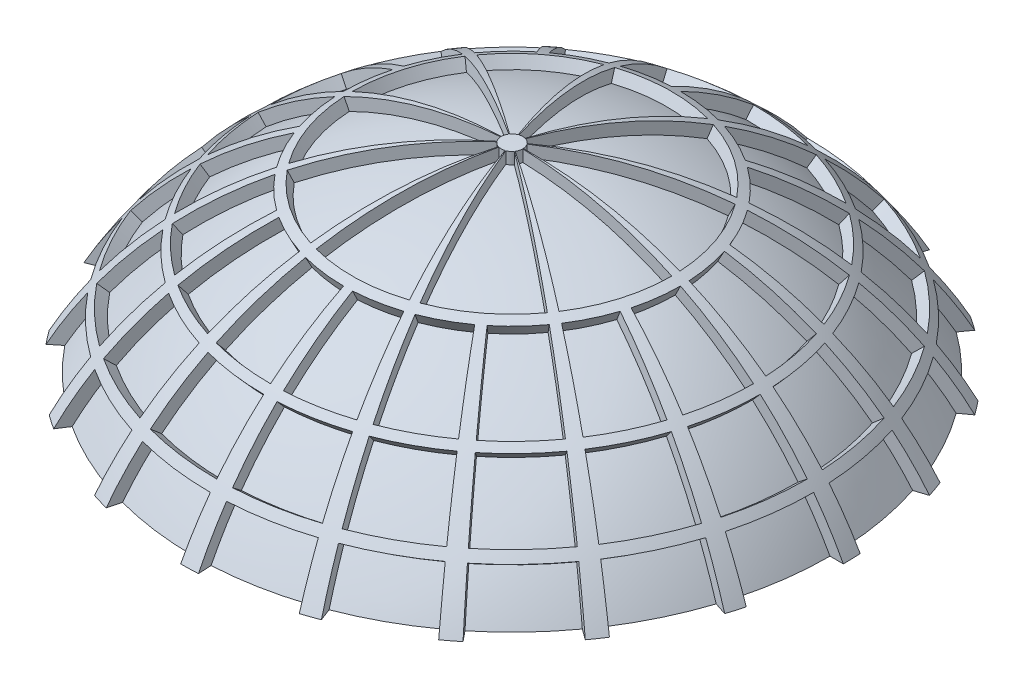
SolidWorks part; units mm, degrees
note: The reader was unsure of these and kept them because the rebuilt part matched: shared geometry of "草图1<3>", "草图1<5>".
ref_plane "前视基准面" through (0, 0, 0) normal (0, 0, 1) x (1, 0, 0)
ref_plane "上视基准面" through (0, 0, 0) normal (0, 1, 0) x (1, 0, 0)
ref_plane "右视基准面" through (0, 0, 0) normal (1, 0, 0) x (0, 0, -1)
sketch "草图1" plane through (0, 0, 0) normal (0, 0, 1) x (1, 0, 0)
  line L0 (0, 300) -> (0, 150)
  line L1 (0, 300) -> (0, 765.499)
  line L2 (0, -300) -> (0, -863.1339)
  line L3 (-10, -300) -> (-10, -863.1339)
  line L4 (0, 150) -> (996.1607, 150)
  line L5 (139.286, 276.9466) -> (143.7791, 285.8803)
  line L6 (132.0893, 280.4504) -> (136.3503, 289.4972)
  line L7 (211.8031, 239.8738) -> (205.1842, 232.3778)
  line L8 (206.0532, 244.8307) -> (199.6141, 237.1797)
  line L9 (257.3478, 190.1897) -> (249.3057, 184.2463)
  line L10 (251.9239, 197.3179) -> (244.0512, 191.1518)
  line L11 (9.174, 319.8685) -> (9.174, 309.8642)
  arc A0 (259.8076, 150) -> (0, 300) centre (0, 0) ccw
  arc A1 (271.2932, 150) -> (0, 310) centre (0, 0) ccw
  arc A2 (282.6659, 150) -> (0, 320) centre (0, 0) ccw
  arc A3 (0, -300) -> (0, 300) centre (0, 0) ccw construction
  arc A4 (0, -310) -> (0, 310) centre (0, 0) ccw construction
  arc A5 (0, -320) -> (0, 320) centre (0, 0) ccw construction
  dimension "D1" = 600
  dimension "D2" = 10
  dimension "D4" = 150
  dimension "D3" = 10
revolve "旋转1" add sketch "草图1" angle 360 about L0
revolve "旋转2" add sketch "草图1<3>" angle 3 about L1
sketch "草图1<3>" plane through (0, 0, 0) normal (0, 0, 1) x (1, 0, 0) same geometry as "草图1"
revolve "旋转3" add sketch "草图1<5>" angle 3 about L1
sketch "草图1<5>" plane through (0, 0, 0) normal (0, 0, 1) x (1, 0, 0) same geometry as "草图1"
pattern_circular "阵列(圆周)3" count 20 over 360 about axis through (0, 0, 0) along (0, 1, 0) of "旋转3"
pattern_circular "阵列(圆周)4" count 10 over 360 about axis through (0, 0, 0) along (0, 1, 0) of "旋转2"
equation "\"‘\"=20"
